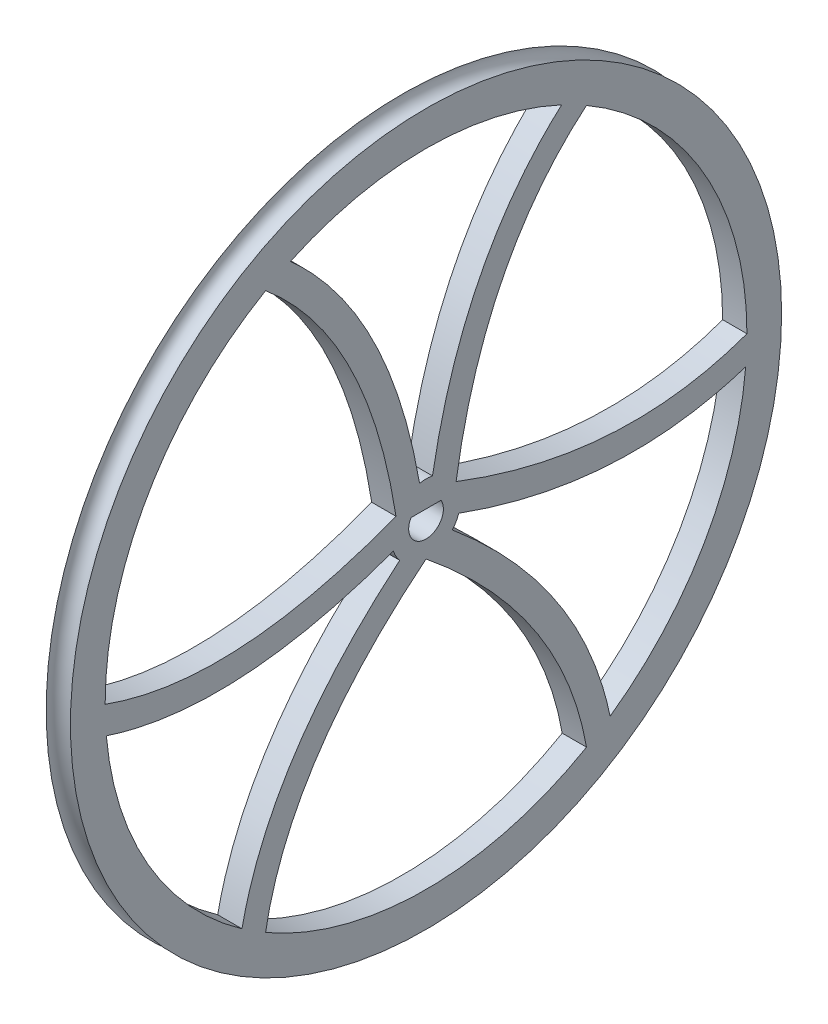
SolidWorks part; units mm, degrees
ref_plane "Front Plane" through (0, 0, 0) normal (0, 0, 1) x (1, 0, 0)
ref_plane "Top Plane" through (0, 0, 0) normal (0, 1, 0) x (1, 0, 0)
ref_plane "Right Plane" through (0, 0, 0) normal (1, 0, 0) x (0, 0, -1)
sketch "Sketch1" plane through (0, 0, 0) normal (0, 0, 1) x (1, 0, 0)
  line L0 (0, 0) -> (-8.3638, 0) construction
  line L1 (-1.778, 46.99) -> (1.778, 46.99)
  line L2 (-1.778, 46.99) -> (-1.778, 52.07)
  line L4 (1.778, 46.99) -> (1.778, 52.07)
  arc A0 (-1.778, 52.07) -> (1.778, 52.07) centre (0, 52.07) ccw
  point P7 (0, 46.99)
  dimension "D1" = 1.778
  dimension "D2" = 5.08
  dimension "D3" = 52.07
  dimension "D4" = 8.3638
revolve "Revolve1" add sketch "Sketch1" angle 360 about L0
sketch "Sketch3" plane through (0, 0, 0) normal (1, 0, 0) x (0, 0, -1)
  line L0 (2.1997, 1.27) -> (-2.1997, 1.27)
  circle A0 centre (0, 0) radius 2.54
  circle A1 centre (0, 0) radius 5.08
  dimension "D1" = 5.08
  dimension "D2" = 10.16
  dimension "D3" = 1.27
extrude "Boss-Extrude1" add sketch "Sketch3" along normal mid plane 3.556 separate body contours L0 A0 | A1 A0 region at (0, 1.7908, 0) region at (0, 0, 4.9363)
sketch "Sketch4" plane through (0, 0, 0) normal (1, 0, 0) x (0, 0, -1)
  line L0 (-4.3994, 2.54) -> (0, -5.08) construction
  line L1 (0, -5.08) -> (4.3994, 2.54) construction
  line L2 (4.3994, 2.54) -> (-4.3994, 2.54) construction
  line L3 (0, 0) -> (0, 46.99) construction
  line L4 (73.7975, 82.9097) -> (-28.4615, -2.8958) construction
  circle A0 centre (0, 0) radius 5.08 construction
  circle A1 centre (0, 0) radius 5.08
  circle A2 centre (0, 0) radius 46.99 construction
  circle A3 centre (0, 0) radius 46.99
  spline S0 degree 2 poles (4.3994, 2.54) (8.4039, 28.0379) (23.4905, 40.6971) knots 0 0 0 0.590133 0.590133 0.590133
  spline S1 degree 2 poles (-4.3994, 2.54) (-8.4039, 28.0379) (-23.4905, 40.6971) knots 0 0 0 0.590133 0.590133 0.590133
  spline S2 degree 1 poles (-0.6355, 3.1311) (-21.0415, 43.6157) knots 0 0 1 1 construction
  spline S3 degree 3 poles (-0.6355, 3.1311) (-0.8065, 4.2199) (-1.186, 6.4106) (-2.06, 10.6191) (-3.3864, 15.6591) (-5.3535, 21.3202) (-8.4851, 28.3572) (-13.3737, 36.1796) (-18.3098, 41.3236) (-21.0415, 43.6157) knots 0 0 0 0 0.036883 0.073767 0.147533 0.2213 0.295067 0.4426 0.590133 0.590133 0.590133 0.590133
  spline S4 degree 1 poles (0.6355, 3.1311) (21.0415, 43.6157) knots 0 0 1 1 construction
  spline S5 degree 3 poles (0.6355, 3.1311) (0.8065, 4.2199) (1.186, 6.4106) (2.06, 10.6191) (3.3864, 15.6591) (5.3535, 21.3202) (8.4851, 28.3572) (13.3737, 36.1796) (18.3098, 41.3236) (21.0415, 43.6157) knots 0 0 0 0 0.036883 0.073767 0.147533 0.2213 0.295067 0.4426 0.590133 0.590133 0.590133 0.590133
  point P6 (4.3994, 2.54)
  point P7 (-4.3994, 2.54)
  point P8 (0, -5.08)
  dimension "D2" = 39.3883
  dimension "D4" = 43.6174
  dimension "D1" = 60
  dimension "D3" = 40
  dimension "D5" = 3.81
  dimension "D6" = 3.81
extrude "Boss-Extrude2" add sketch "Sketch4" along normal mid plane 3.556 contours A1 S3 A3 S1 | S5 A1 S0 A3 region at (0, 24.0306, -10.0481) region at (0, 24.0306, 10.0481)
pattern_circular "CirPattern1" count 3 over 360 about axis through (1.778, 0, 0) along (1, 0, 0) of "Boss-Extrude2"
